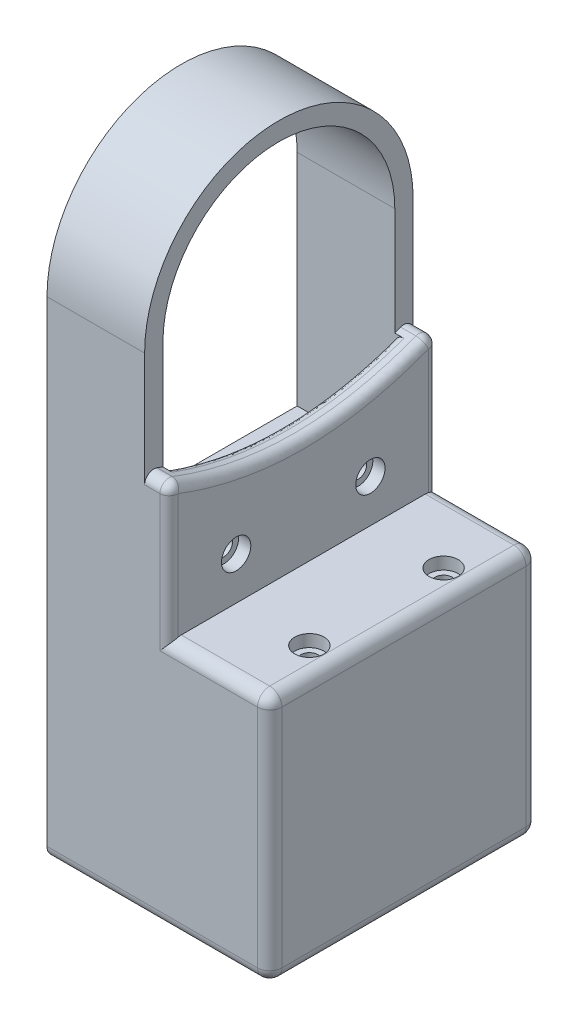
SolidWorks part; units mm, degrees
ref_plane "Front Plane" through (0, 0, 0) normal (0, 0, 1) x (1, 0, 0)
ref_plane "Top Plane" through (0, 0, 0) normal (0, 1, 0) x (1, 0, 0)
ref_plane "Right Plane" through (0, 0, 0) normal (1, 0, 0) x (0, 0, -1)
sketch "Sketch1" plane through (0, 0, 0) normal (1, 0, 0) x (0, 0, -1)
  line L0 (-22, 0) -> (-22, -39)
  line L1 (-22, -39) -> (22, -39)
  line L2 (22, -39) -> (22, 0)
  line L4 (-19, 0) -> (-19, -36)
  line L6 (19, 0) -> (19, -36)
  line L7 (19, -36) -> (-19, -36)
  arc A2 (-19, 0) -> (19, 0) centre (0, 0) cw
  arc A3 (-22, 0) -> (22, 0) centre (0, 0) cw
  dimension "D1" = 36
  dimension "D2" = 3
  dimension "D3" = 3
  dimension "D4" = 19
extrude "Boss-Extrude1" add sketch "Sketch1" along normal blind 16
sketch "Sketch2" plane through (16, 0, 0) normal (1, 0, 0) x (0, 0, -1)
  line L0 (-22, -16.4659) -> (-22, -39)
  line L1 (-22, 0) -> (-22, -39) construction
  line L2 (-22, -39) -> (22, -39)
  line L3 (22, -39) -> (22, -16.4659)
  line L4 (22, -39) -> (22, 0) construction
  spline S0 degree 2 poles (-22, -16.4659) (0, -25.8143) (22, -16.4659) knots 0 0 0 1 1 1
extrude "Boss-Extrude2" add sketch "Sketch2" along normal blind 4
sketch "Sketch3" plane through (20, 0, 0) normal (1, 0, 0) x (0, 0, -1)
  circle A0 centre (-11, -32) radius 1.4
  circle A1 centre (11, -32) radius 1.4
  dimension "D1" = 2.8
  dimension "D2" = 2.8
  dimension "D3" = 11
  dimension "D4" = 11
  dimension "D5" = 32
  dimension "D6" = 32
extrude "Cut-Extrude1" cut sketch "Sketch3" against normal blind 10
sketch "Sketch4" plane through (20, 0, 0) normal (1, 0, 0) x (0, 0, -1)
  circle A0 centre (-11, -32) radius 2.4
  circle A1 centre (11, -32) radius 2.4
  dimension "D1" = 4.8
  dimension "D2" = 4.8
extrude "Cut-Extrude2" cut sketch "Sketch4" against normal blind 2
sketch "Sketch5" plane through (0, 0, 0) normal (1, 0, 0) x (0, 0, -1)
  line L0 (22, -39) -> (-22, -39)
  line L1 (-22, -39) -> (-22, -80)
  line L2 (-22, -80) -> (22, -80)
  line L3 (22, -80) -> (22, -39)
  line L4 (19, -42) -> (-19, -42)
  line L5 (-19, -42) -> (-19, -77)
  line L6 (-19, -77) -> (19, -77)
  line L7 (19, -77) -> (19, -42)
  dimension "D1" = 3
  dimension "D2" = 3
  dimension "D3" = 3
  dimension "D4" = 3
  dimension "D5" = 35
extrude "Boss-Extrude3" add sketch "Sketch5" along normal blind 35.5
sketch "Sketch6" plane through (0, -77, 0) normal (0, 1, 0) x (1, 0, 0)
  circle A0 centre (32, 11) radius 1.4
  circle A1 centre (32, -11) radius 1.4
  dimension "D1" = 2.8
  dimension "D2" = 2.8
  dimension "D3" = 11
  dimension "D4" = 11
  dimension "D5" = 32
  dimension "D6" = 32
extrude "Cut-Extrude3" cut sketch "Sketch6" against normal up to next and the other way up to surface other way up to face at (27.75, -39, 0)
sketch "Sketch7" plane through (0, -80, 0) normal (0, -1, 0) x (1, 0, 0)
  circle A0 centre (32, 11) radius 2.4
  circle A1 centre (32, -11) radius 2.4
  dimension "D1" = 4.8
  dimension "D2" = 4.8
extrude "Cut-Extrude4" cut sketch "Sketch7" against normal blind 2
sketch "Sketch9" plane through (0, -39, 0) normal (0, 1, 0) x (1, 0, 0)
  line L0 (35.5, 22) -> (36.5, 22)
  line L1 (36.5, 22) -> (36.5, -22)
  line L2 (36.5, -22) -> (35.5, -22)
  line L3 (35.5, -22) -> (35.5, 22)
  dimension "D1" = 1
extrude "Boss-Extrude4" add sketch "Sketch9" against normal up to surface (41 mm away) up to face at (32, -80, 8.6)
sketch "Sketch10" plane through (0, -39, 0) normal (0, 1, 0) x (1, 0, 0)
  circle A0 centre (32, 11) radius 2.4
  circle A1 centre (32, -11) radius 2.4
  dimension "D1" = 4.8
  dimension "D2" = 4.8
extrude "Cut-Extrude6" cut sketch "Sketch10" against normal blind 2
sketch "Sketch11" plane through (0, -80, 0) normal (0, -1, 0) x (1, 0, 0)
  line L0 (0, 22) -> (0, -22) construction
  line L1 (0, 12.5) -> (0, -12.5)
  arc A0 (0, 12.5) -> (0, -12.5) centre (0, 0) cw
  dimension "D1" = 12.5
extrude "Cut-Extrude7" cut sketch "Sketch11" against normal up to next
fillet "Fillet1" radius 1 4 edges at (12.5, -77, 0) (0, -78.5, 12.5) (12.5, -80, 0) (0, -78.5, -12.5)
fillet "Fillet2" radius 1.5 6 edges at (18, -16.4659, 22) (18, -16.4659, -22) (20, -27.733, -22) (20, -27.733, 22)
sketch "Sketch12" plane through (0, 0, 0) normal (-1, 0, 0) x (0, 0, 1)
  line L0 (-22, -80) -> (-22, 0) construction
  line L1 (22, 0) -> (22, -80) construction
  line L2 (19, -77) -> (-19, -77) construction
  line L3 (19, -77) -> (13.5, -77) construction
  line L4 (-19, -42) -> (19, -42) construction
  line L5 (19, -36) -> (-19, -36) construction
  line L6 (-13.5, -80) -> (-22, -80) construction
  line L7 (22, -80) -> (13.5, -80) construction
  circle A0 centre (-20.5, -16) radius 1
  circle A1 centre (20.5, -16) radius 1
  circle A2 centre (20.5, -60) radius 1
  circle A3 centre (-20.5, -60) radius 1
  circle A4 centre (-17, -78.5) radius 1
  circle A5 centre (17, -78.5) radius 1
  circle A6 centre (-11, -39) radius 1
  circle A7 centre (11, -39) radius 1
  dimension "D1" = 2
  dimension "D2" = 2
  dimension "D3" = 2
  dimension "D4" = 2
  dimension "D5" = 2
  dimension "D6" = 2
  dimension "D7" = 2
  dimension "D8" = 2
  dimension "D9" = 1.5
  dimension "D10" = 1.5
  dimension "D11" = 1.5
  dimension "D12" = 1.5
  dimension "D13" = 1.5
  dimension "D14" = 1.5
  dimension "D15" = 3
  dimension "D16" = 3
  dimension "D17" = 20
  dimension "D18" = 20
  dimension "D19" = 5
  dimension "D20" = 5
  dimension "D21" = 11
  dimension "D22" = 11
  dimension "D23" = 20
  dimension "D24" = 20
extrude "Cut-Extrude8" cut sketch "Sketch12" against normal blind 4
fillet "Fillet3" radius 2 8 edges at (36.5, -59.5, -22) (36.5, -59.5, 22) (36.5, -80, 0) (36.5, -39, 0) (27.5, -39, -22) (27.5, -39, 22) (18.25, -80, -22) (18.25, -80, 22)
sketch "Sketch13" plane through (0, 0, -22) normal (0, 0, -1) x (-1, 0, 0)
  line L1 (-11.5, -47) -> (-7, -47)
  line L2 (-11.5, -47) -> (-11.5, -58)
  line L3 (-11.5, -58) -> (-7, -58)
  line L4 (-7, -47) -> (-7, -58)
  line L5 (-11.5, -47) -> (-7, -58) construction
  line L6 (-11.5, -58) -> (-7, -47) construction
  line L7 (-34.5, -78) -> (0, -78) construction
  line L8 (0, -78) -> (0, 0) construction
  point P0 (-9.25, -52.5)
  dimension "D1" = 11
  dimension "D2" = 4.5
  dimension "D3" = 20
  dimension "D4" = 7
extrude "Cut-Extrude9" cut sketch "Sketch13" against normal up to next
